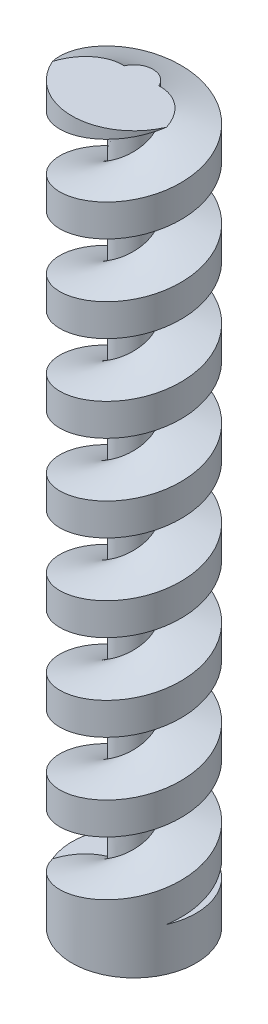
SolidWorks part; units mm, degrees
note: The reader was unsure of these and kept them because the rebuilt part matched: shared geometry of "Sketch1<3>".
ref_plane "Front Plane" through (0, 0, 0) normal (0, 0, 1) x (1, 0, 0)
ref_plane "Top Plane" through (0, 0, 0) normal (0, 1, 0) x (1, 0, 0)
ref_plane "Right Plane" through (0, 0, 0) normal (1, 0, 0) x (0, 0, -1)
sketch "Sketch1" plane through (0, 0, 0) normal (0, 1, 0) x (1, 0, 0)
  circle A0 centre (0, 0) radius 9.1281
  dimension "D1" = 18.2562
extrude "Boss-Extrude1" add sketch "Sketch1" along normal blind 9.525
extrude "Boss-Extrude2" add sketch "Sketch1<3>" along normal blind 101.6
sketch "Sketch1<3>" plane through (0, 0, 0) normal (0, 1, 0) x (1, 0, 0) same geometry as "Sketch1"
sketch "Sketch4" plane through (0, 0, 0) normal (1, 0, 0) x (0, 0, -1)
  line L0 (9.1281, 101.6) -> (2.7781, 101.6)
  line L1 (9.1281, 101.6) -> (-9.1281, 101.6) construction
  line L2 (2.7781, 101.6) -> (2.7781, 0)
  line L3 (-9.1281, 0) -> (9.1281, 0) construction
  line L4 (2.7781, 0) -> (9.1281, 0)
  line L5 (2.7781, 2.3539) -> (9.1281, 3.9963)
  line L6 (9.1281, 0) -> (9.1281, 101.6) construction
  line L7 (9.1281, 3.9963) -> (9.1281, -3.9961)
  line L9 (2.7781, -2.3539) -> (2.7781, 2.3539)
  line L12 (2.7781, -2.3539) -> (9.1281, -3.9961)
  dimension "D1" = 6.35
  dimension "D2" = 29
  dimension "D3" = 4.7079
  dimension "D4" = 2.3539
  dimension "D5" = 3.9961
sketch "Sketch5" plane through (0, 0, 0) normal (0, -1, 0) x (1, 0, 0)
  circle A0 centre (0, 0) radius 6.35
curve "Helix/Spiral1" pitch 12.7 height 127 turns 10
sweep "Cut-Sweep2" cut profiles "Sketch4" path "Helix/Spiral1"
sketch "Sketch6" plane through (0, 0, 0) normal (0, -1, 0) x (1, 0, 0)
  circle A0 centre (0, 0) radius 9.1281
  dimension "D1" = 18.2562
extrude "Boss-Extrude3" add sketch "Sketch6" along normal blind 6.35
sketch "Sketch2" plane through (0, -6.35, 0) normal (0, -1, 0) x (1, 0, 0)
  line L0 (-1.5, 2) -> (-1.5, -2)
  line L1 (1.5, 2) -> (1.5, -2)
  circle A0 centre (0, 0) radius 2.5
  dimension "D1" = 5
  dimension "D2" = 3
  dimension "D3" = 1.5
extrude "Cut-Extrude1" cut sketch "Sketch2" against normal blind 5.5562 contours L1 A0 L0
